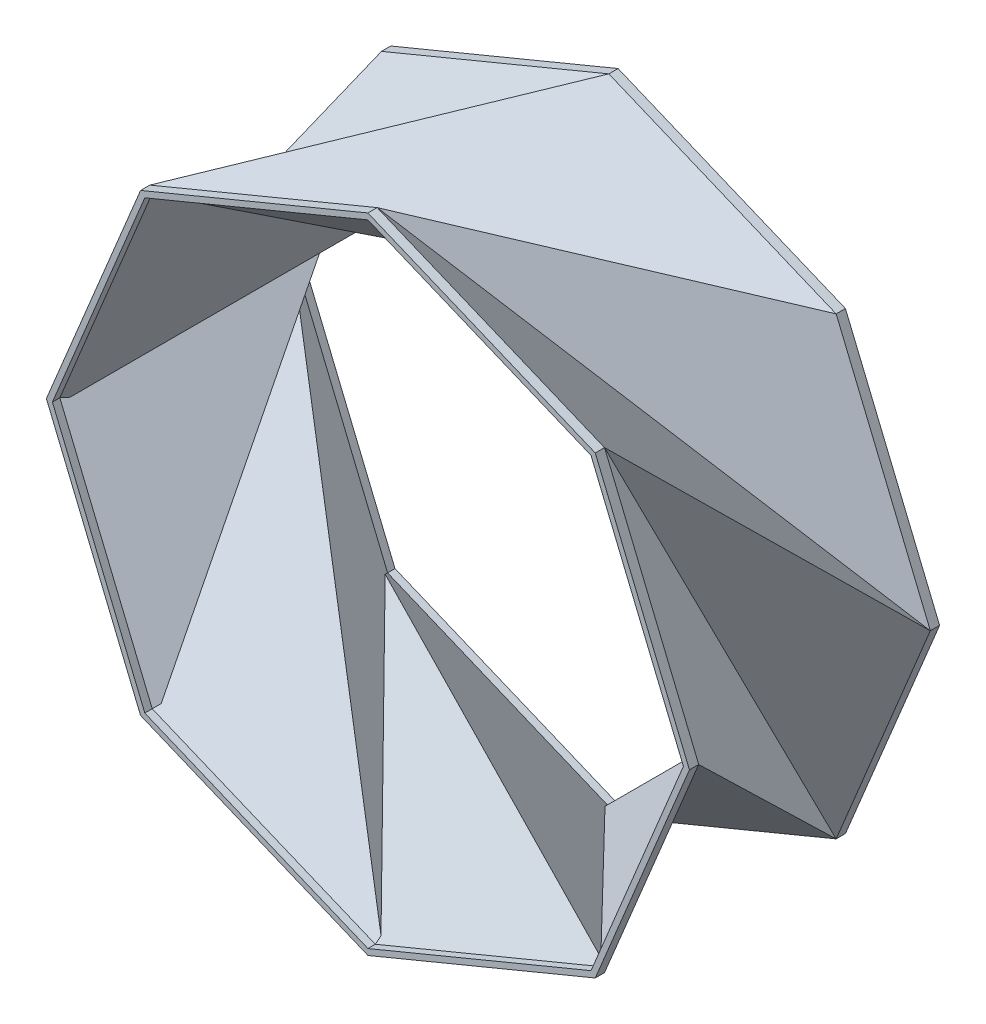
SolidWorks part; units mm, degrees
ref_plane "정면" through (0, 0, 0) normal (0, 0, 1) x (1, 0, 0)
ref_plane "윗면" through (0, 0, 0) normal (0, 1, 0) x (1, 0, 0)
ref_plane "우측면" through (0, 0, 0) normal (1, 0, 0) x (0, 0, -1)
sketch "스케치1" plane through (0, 0, 0) normal (0, 0, 1) x (1, 0, 0)
  line L0 (-25.4558, -25.4558) -> (25.4558, 25.4558) construction
  line L1 (25.4558, -25.4558) -> (36, 0)
  line L2 (36, 0) -> (25.4558, 25.4558)
  line L3 (25.4558, 25.4558) -> (0, 36)
  line L4 (0, 36) -> (-25.4558, 25.4558)
  line L5 (-25.4558, 25.4558) -> (-36, 0)
  line L6 (-36, 0) -> (-25.4558, -25.4558)
  line L7 (-25.4558, -25.4558) -> (0, -36)
  line L8 (0, -36) -> (25.4558, -25.4558)
  line L9 (24.5374, -24.5374) -> (34.7011, 0)
  line L10 (34.7011, 0) -> (24.5374, 24.5374)
  line L11 (24.5374, 24.5374) -> (0, 34.7011)
  line L12 (0, 34.7011) -> (-24.5374, 24.5374)
  line L13 (-24.5374, 24.5374) -> (-34.7011, 0)
  line L14 (-34.7011, 0) -> (-24.5374, -24.5374)
  line L15 (-24.5374, -24.5374) -> (0, -34.7011)
  line L16 (0, -34.7011) -> (24.5374, -24.5374)
  circle A0 centre (0, 0) radius 33.2597 construction
  dimension "D1" = 72
  dimension "D2" = 1.2
extrude "보스-돌출1" add sketch "스케치1" along normal blind 25 contours L9 L10 L11 L12 L13 L14 L15 L16
ref_plane "평면1" through (7.8429, -18.9344, 15.3955) normal (0.306, -0.7387, 0.6006) x (-0.952, -0.2374, 0.193)
sketch "스케치2" plane through (7.8429, -18.9344, 15.3955) normal (0.306, -0.7387, 0.6006) x (-0.952, -0.2374, 0.193)
  line L0 (8.238, 21.892) -> (-28.2112, -19.3972)
  line L1 (-28.2112, -19.3972) -> (-17.5355, 15.48)
sketch "스케치3" plane through (12.2687, -29.6193, 0) normal (0.3827, -0.9239, 0) x (0.9239, 0.3827, 0)
  line L0 (-13.2795, 0) -> (13.2795, 25)
ref_plane "평면2" through (0, -34.7011, 0) normal (0.6301, 0.6301, 0.4539) x (0.7765, -0.5112, -0.3683)
sketch "스케치4" plane through (0, -34.7011, 0) normal (0.6301, 0.6301, 0.4539) x (0.7765, -0.5112, -0.3683)
  line L0 (0, 0) -> (4.6512, -14.3431) construction
  line L1 (0, 0) -> (13.8586, 5.9411) construction
  line L2 (0, 0) -> (4.6512, -14.3431)
  line L3 (0, 0) -> (13.8586, 5.9411)
  line L4 (13.8586, 5.9411) -> (4.6512, -14.3431)
extrude "컷-돌출1" cut sketch "스케치4" along normal up to vertex (55.0757 mm away) up to point (34.7011, 0, 25)
pattern_circular "원형 패턴1" count 8 over 360 about axis through (0, 0, 25) along (0, 0, 1) of "컷-돌출1"
sketch "스케치5" plane through (0, 0, 25) normal (0, 0, 1) x (1, 0, 0)
  line L8 (0, -34.7011) -> (24.5374, -24.5374)
  line L10 (0, -34.7011) -> (24.5374, -24.5374)
  line L12 (24.5374, -24.5374) -> (34.7011, 0)
  line L14 (24.5374, -24.5374) -> (34.7011, 0)
  line L24 (34.7011, 0) -> (24.5374, 24.5374)
  line L26 (34.7011, 0) -> (24.5374, 24.5374)
  line L28 (24.5374, 24.5374) -> (0, 34.7011)
  line L30 (24.5374, 24.5374) -> (0, 34.7011)
  line L32 (0, 34.7011) -> (-24.5374, 24.5374)
  line L33 (0, 34.7011) -> (-24.5374, 24.5374)
  line L34 (-24.5374, 24.5374) -> (-34.7011, 0)
  line L35 (-24.5374, 24.5374) -> (-34.7011, 0)
  line L36 (-34.7011, 0) -> (-24.5374, -24.5374)
  line L37 (-34.7011, 0) -> (-24.5374, -24.5374)
  line L38 (-24.5374, -24.5374) -> (0, -34.7011)
  line L39 (-24.5374, -24.5374) -> (0, -34.7011)
  dimension "D1" = 0
extrude "보스-돌출2" add sketch "스케치5" along normal blind 1
sketch "스케치6" plane through (0, 0, 0) normal (0, 0, -1) x (-1, 0, 0)
  line L8 (-24.5374, -24.5374) -> (0, -34.7011)
  line L10 (-24.5374, -24.5374) -> (0, -34.7011)
  line L12 (0, -34.7011) -> (24.5374, -24.5374)
  line L14 (0, -34.7011) -> (24.5374, -24.5374)
  line L24 (24.5374, -24.5374) -> (34.7011, 0)
  line L26 (24.5374, -24.5374) -> (34.7011, 0)
  line L28 (34.7011, 0) -> (24.5374, 24.5374)
  line L30 (34.7011, 0) -> (24.5374, 24.5374)
  line L32 (24.5374, 24.5374) -> (0, 34.7011)
  line L33 (24.5374, 24.5374) -> (0, 34.7011)
  line L34 (0, 34.7011) -> (-24.5374, 24.5374)
  line L35 (0, 34.7011) -> (-24.5374, 24.5374)
  line L36 (-24.5374, 24.5374) -> (-34.7011, 0)
  line L37 (-24.5374, 24.5374) -> (-34.7011, 0)
  line L38 (-34.7011, 0) -> (-24.5374, -24.5374)
  line L39 (-34.7011, 0) -> (-24.5374, -24.5374)
  dimension "D1" = 0
extrude "보스-돌출3" add sketch "스케치6" along normal blind 1
shell "쉘1" thickness 0.6 removed face at (0, 0, -1) removed face at (0, 0, 26)
